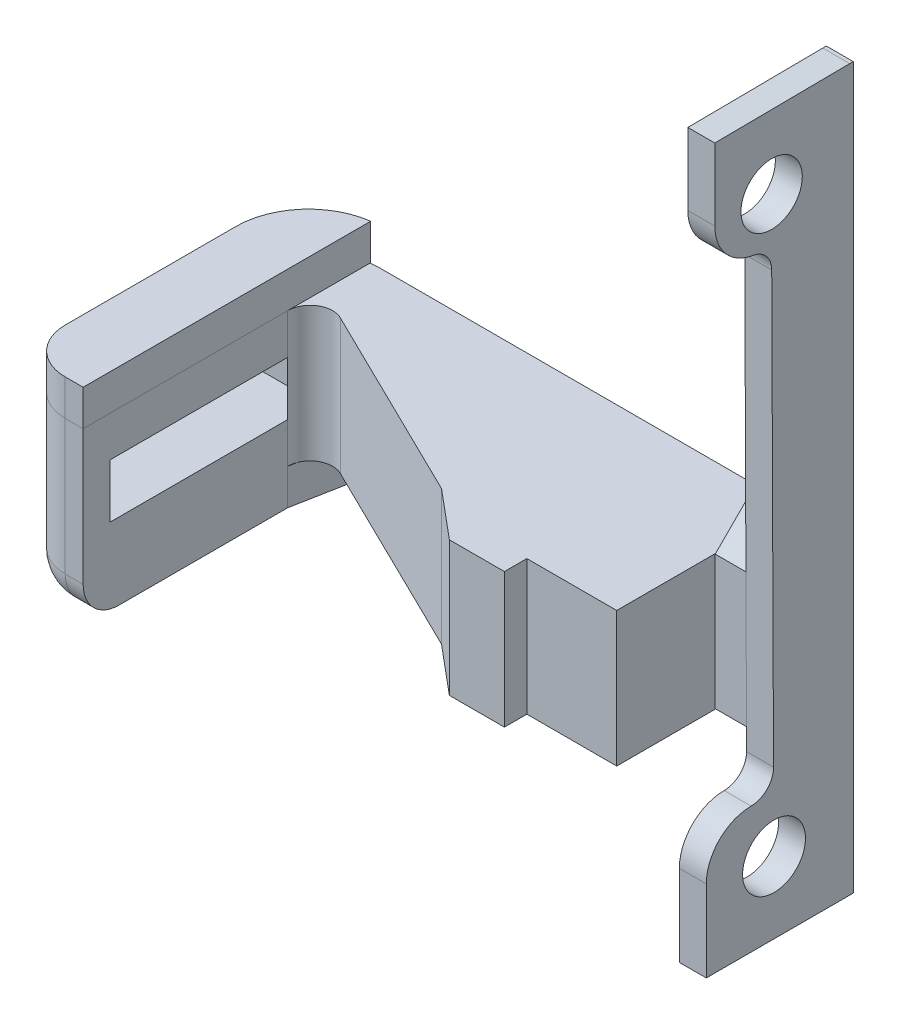
SolidWorks part; units mm, degrees
ref_plane "Front Plane" through (0, 0, 0) normal (0, 0, 1) x (1, 0, 0)
ref_plane "Top Plane" through (0, 0, 0) normal (0, 1, 0) x (1, 0, 0)
ref_plane "Right Plane" through (0, 0, 0) normal (1, 0, 0) x (0, 0, -1)
sketch "Sketch1" plane through (0, 0, 0) normal (1, 0, 0) x (0, 0, -1)
  line L0 (0, 0) -> (-4.8, 0) construction
  line L1 (0.4003, 1.5) -> (-4.8, 1.5)
  line L2 (0.4003, -1.5) -> (-4.8, -1.5)
  line L3 (0, 1.5) -> (-4.8, 1.5) construction
  line L4 (-4.8, -1.5) -> (-4.8, 1.5)
  line L5 (0, -1.5) -> (-4.8, -1.5) construction
  line L8 (0.4003, 1.5) -> (0.4003, -1.5)
  dimension "D1" = 1.5
  dimension "D2" = 1.5
extrude "Boss-Extrude1" [suppressed] add sketch "Sketch1" along normal blind 10.54
sketch "Sketch2" [suppressed] plane through (0, 0, 0) normal (-1, 0, 0) x (0, 0, 1)
  line L0 (4.8, 0) -> (0, 0) construction
  line L1 (4.8, 1.5) -> (4.8, -1.5) construction
  line L2 (4.8, 0.69) -> (0, 0.69)
  line L3 (4.8, -0.69) -> (0, -0.69)
  line L4 (4.8, -0.69) -> (4.8, 0.69)
  line L5 (4.8, 0.69) -> (0, 0.69) construction
  line L6 (4.8, -0.69) -> (0, -0.69) construction
  line L10 (0, 0.69) -> (0, -0.69)
  dimension "D1" = 0.69
  dimension "D2" = 0.69
extrude "Cut-Extrude1" [suppressed] cut sketch "Sketch2" against normal blind 1.54
sketch "Sketch3" [suppressed] plane through (0, 1.5, 0) normal (0, 1, 0) x (1, 0, 0)
  line L0 (4.7634, -2.5645) -> (2.8416, -4.8)
  line L1 (10.7634, -2.5645) -> (4.7634, -2.5645)
  line L2 (10.7634, -2.5645) -> (10.7634, -4.8)
  line L3 (2.8416, -4.8) -> (10.7634, -4.8)
  line L5 (10.54, -4.8) -> (0, -4.8) construction
extrude "Cut-Extrude2" [suppressed] cut sketch "Sketch3" against normal blind 5
fillet "Fillet1" [suppressed] radius 1
sketch "Sketch4" [suppressed] plane through (0, 0.69, 0) normal (0, -1, 0) x (1, 0, 0)
  circle A0 centre (0.5902, 1.1045) radius 0.31
  circle A1 centre (0.5902, 2.2049) radius 0.3 construction
  circle A2 centre (0.5902, 3.386) radius 0.31
extrude "Cut-Extrude3" [suppressed] cut sketch "Sketch4" against normal blind 10 and the other way blind 10
fillet "Fillet2" [suppressed] radius 2
sketch "Sketch5" [suppressed] plane through (0, -1.5, 0) normal (0, -1, 0) x (1, 0, 0)
  line L0 (10.54, 0) -> (1, 0) construction
  line L1 (10.54, 2.5645) -> (6.24, 2.5645)
  line L2 (10.54, 2.5645) -> (10.54, 0)
  line L3 (10.54, 0) -> (6.24, 0)
  line L4 (6.24, 2.5645) -> (6.24, 0)
extrude "Boss-Extrude2" [suppressed] add sketch "Sketch5" along normal blind 3 and the other way blind 6
sketch "Sketch6" [suppressed] plane through (0, 0, 2.5645) normal (0, 0, 1) x (1, 0, 0)
  line L1 (10.54, 4.5) -> (6.24, 4.5)
  line L2 (10.54, 4.5) -> (10.54, -4.5)
  line L3 (10.54, -4.5) -> (6.24, -4.5)
  line L4 (6.24, 4.5) -> (6.24, -4.5)
extrude "Boss-Extrude3" [suppressed] add sketch "Sketch6" along normal blind 0.9
fillet "Fillet4" [suppressed] radius 2
fillet "Fillet5" [suppressed] radius 1
sketch "Sketch9" [suppressed] plane through (0, 4.5, 0) normal (0, 1, 0) x (1, 0, 0)
  line L1 (10.54, -3.4645) -> (8.54, -3.4645)
  line L2 (10.54, -3.4645) -> (10.54, -2.9645)
  line L3 (10.54, -2.9645) -> (8.54, -2.9645)
  line L4 (8.54, -3.4645) -> (8.54, -2.9645)
extrude "Cut-Extrude4" [suppressed] cut sketch "Sketch9" against normal blind 11
sketch "Sketch12" plane through (0, 0, 0) normal (0, 1, 0) x (1, 0, 0)
  line L0 (0.7, -5.4) -> (1.0988, -5.4)
  line L1 (1.3, 1.0003) -> (1.6, 1.0003)
  line L2 (10.54, 1.0003) -> (1.6, 1.0003)
  line L3 (-0.3, -0.5997) -> (-0.3, -4.4)
  line L4 (1.0988, -5.4) -> (1.0988, -0.8471)
  line L5 (6.24, -2.5645) -> (1.8346, -0.4062)
  line L6 (6.24, -2.5645) -> (7.3148, -3.4645)
  line L7 (7.3148, -3.4645) -> (8.54, -3.4645)
  line L10 (6.24, -2.5645) -> (6.24, 0) construction
  line L12 (8.24, 0) -> (6.24, 0) construction
  line L14 (8.24, 0) -> (8.24, -3.4645) construction
  line L18 (10.54, -2.9645) -> (8.54, -2.9645)
  line L21 (10.54, -2.9645) -> (10.54, 1.0003)
  line L24 (8.54, -3.4645) -> (8.54, -2.9645)
  arc A0 (1.8346, -0.4062) -> (1.0988, -0.8471) centre (1.5988, -0.8471) ccw
  arc A4 (-0.3, -4.4) -> (0.7, -5.4) centre (0.7, -4.4) ccw
  arc A5 (1.3, 1.0003) -> (-0.3, -0.5997) centre (1.3, -0.5997) ccw
  circle A6 centre (0.5902, -3.386) radius 0.31 construction
  circle A7 centre (0.5902, -1.1045) radius 0.31 construction
  dimension "D1" = 0.5
extrude "Boss-Extrude5" add sketch "Sketch12" along normal blind 3
sketch "Sketch13" plane through (-0.3, 0, 0) normal (-1, 0, 0) x (0, 0, 1)
  line L0 (0.2, 0.9) -> (0.2, 2.1)
  line L1 (4.8, 0.9) -> (4.8, 2.1)
  line L4 (4.8, 1.5) -> (0.2, 1.5) construction
  line L5 (4.8, 2.1) -> (0.2, 2.1)
  line L6 (4.8, 0.9) -> (0.2, 0.9)
  dimension "D1" = 0.6
  dimension "D2" = 0.6
extrude "Cut-Extrude5" cut sketch "Sketch13" against normal up to surface (1.3988 mm away) up to face at (1.0988, 1.5, 3.1235)
sketch "Sketch14" plane through (10.54, 0, 0) normal (1, 0, 0) x (0, 0, -1)
  line L0 (-2.9645, 0) -> (1.0003, 0) construction
  line L1 (1.0003, 3) -> (-0.7721, 3)
  line L2 (1.0003, 3) -> (1.0003, 0)
  line L3 (1.0003, 0) -> (-0.7721, 0)
  line L4 (-0.7721, 3) -> (-0.7721, 0)
  line L5 (-2.5645, 0) -> (0, 0) construction
extrude "Boss-Extrude6" add sketch "Sketch14" along normal blind 0.7
sketch "Sketch15" plane through (0, 0, 0) normal (0, -1, 0) x (1, 0, 0)
  line L0 (-0.3, 0.5997) -> (-0.3, 4.4) construction
  line L1 (0.7, 5.4) -> (1.0988, 5.4) construction
  line L2 (1.0988, 5.4) -> (1.0988, 0.8471) construction
  line L3 (-0.3, 0.5997) -> (-0.3, 4.4)
  line L4 (0.7, 5.4) -> (1.0988, 5.4)
  line L5 (1.0988, 5.4) -> (1.0988, 0.8471)
  line L6 (1.0988, 0.8471) -> (1.45, -1.0003)
  line L7 (1.3, -1.0003) -> (1.6, -1.0003) construction
  line L8 (1.45, -1.0003) -> (1.3, -1.0003)
  arc A0 (-0.3, 0.5997) -> (1.3, -1.0003) centre (1.3, 0.5997) ccw construction
  arc A1 (0.7, 5.4) -> (-0.3, 4.4) centre (0.7, 4.4) ccw construction
  arc A2 (-0.3, 0.5997) -> (1.3, -1.0003) centre (1.3, 0.5997) ccw
  arc A3 (0.7, 5.4) -> (-0.3, 4.4) centre (0.7, 4.4) ccw
extrude "Boss-Extrude7" add sketch "Sketch15" along normal blind 0.8
sketch "Sketch16" plane through (0, 3, 0) normal (0, 1, 0) x (1, 0, 0)
  line L0 (0.7, -5.4) -> (1.0988, -5.4) construction
  line L1 (-0.3, -0.5997) -> (-0.3, -4.4) construction
  line L2 (1.0988, -5.4) -> (1.0988, -0.8471) construction
  line L3 (1.0988, -5.4) -> (1.0988, -0.8471)
  line L4 (-0.3, -0.5997) -> (-0.3, -4.4)
  line L5 (0.7, -5.4) -> (1.0988, -5.4)
  line L6 (1.0988, -0.8471) -> (1.0988, 1.0003)
  line L7 (1.3, 1.0003) -> (1.6, 1.0003) construction
  arc A1 (-0.3, -4.4) -> (0.7, -5.4) centre (0.7, -4.4) ccw construction
  arc A2 (-0.3, -4.4) -> (0.7, -5.4) centre (0.7, -4.4) ccw
  arc A3 (1.0988, 1.0003) -> (-0.3, -0.5997) centre (1.3145, -0.5997) ccw
extrude "Boss-Extrude8" add sketch "Sketch16" along normal blind 0.8 separate body
sketch "Sketch17" plane through (0, 3, 0) normal (0, 1, 0) x (1, 0, 0)
  line L0 (11.24, 1.0003) -> (11.24, -0.7721) construction
  line L1 (11.24, -0.7721) -> (10.54, -0.7721) construction
  line L2 (11.24, -0.7721) -> (10.54, -0.7721)
  line L3 (11.24, -0.7721) -> (11.24, 1.0003)
  line L4 (11.24, 1.0003) -> (10.54, 1.0003)
  line L5 (10.54, 1.0003) -> (10.54, -0.7721)
extrude "Boss-Extrude9" add sketch "Sketch17" along normal blind 0.69
sketch "Sketch18" plane through (0, 0, 0) normal (0, -1, 0) x (1, 0, 0)
  line L0 (11.24, 0.7721) -> (10.54, 0.7721)
  line L1 (10.54, 0.7721) -> (10.54, -1.0003)
  line L2 (10.54, -1.0003) -> (11.24, -1.0003)
  line L3 (11.24, -1.0003) -> (11.24, 0.7721)
extrude "Boss-Extrude10" add sketch "Sketch18" along normal blind 0.69
chamfer "Chamfer1" distance 0.7 angle 45 2 edges at (10.89, 3.69, 0.7721) (10.89, -0.69, 0.7721)
fillet "Fillet7" radius 0.8 5 edges at (0.8994, -0.8, 5.4) (1.375, -0.8, -1.0003) (0.1686, -0.8, -0.5317) (-0.3, -0.8, 2.4998) (-0.0071, -0.8, 5.1071)
fillet "Fillet8" [suppressed] radius 0.8
sketch "Sketch19" plane through (11.24, 0, 0) normal (1, 0, 0) x (0, 0, -1)
  line L1 (0.921, 12.2483) -> (-2.0808, 12.219)
  line L2 (-2.0808, 12.219) -> (-2.0808, 9.6356)
  line L3 (-2.0808, 9.6356) -> (-0.8166, 9.6356)
  line L7 (-0.7721, -0.9673) -> (-0.8166, 9.6356)
  line L8 (1.0003, 12.2483) -> (1.0003, -3.7819)
  line L21 (1.0003, 12.2483) -> (0.921, 12.2483)
  line L23 (-0.7721, -0.9673) -> (-2.271, -0.9673)
  line L24 (-2.271, -0.9673) -> (-2.271, -3.7819)
  line L25 (-2.271, -3.7819) -> (1.0003, -3.7819)
  circle A0 centre (-0.8166, 10.6024) radius 0.6831
  circle A1 centre (-0.7629, -2.189) radius 0.7
  line M9 (1.0003, 3.69) -> (-0.0721, 3.69)
  line M10 (-0.0721, 3.69) -> (-0.7721, 2.99)
  line M11 (-0.7721, 2.99) -> (-0.7721, 0.01)
  line M12 (-0.7721, 0.01) -> (-0.0721, -0.69)
  line M13 (-0.0721, -0.69) -> (1.0003, -0.69)
  line M14 (1.0003, -0.69) -> (1.0003, 3.69)
extrude "Boss-Extrude11" add sketch "Sketch19" along normal blind 0.6 separate body contours L24 L25 L8 L21 L1 L2 L3 L7 L23 A1 A0 M13 M12 M11 M10 M9 | M14 M9 M10 M11 M12 M13 region at (11.24, 4.8332, 0.2685) region at (11.24, 1.5, -0.1581)
fillet "Fillet9" radius 0.5 2 edges at (11.54, -0.9673, 0.7721) (11.54, 9.6356, 0.8166)
fillet "Fillet10" radius 1 2 edges at (11.54, -0.9673, 2.271) (11.54, 9.6356, 2.0808)
